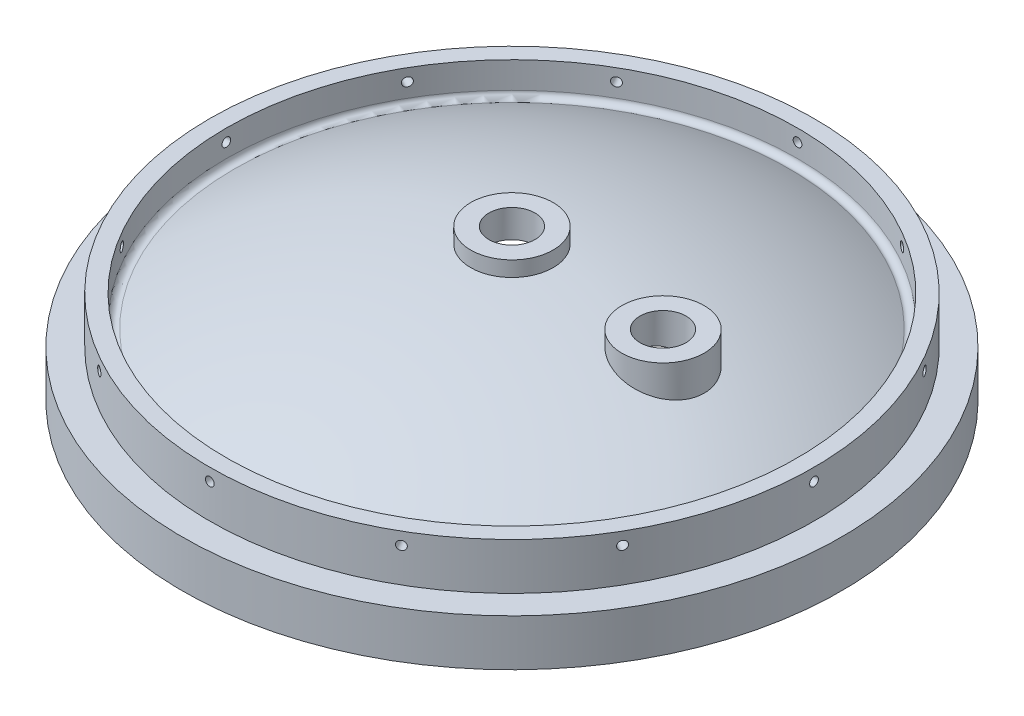
SolidWorks part; units mm, degrees
material "6061-T6 (SS)"
ref_plane "Front Plane" through (0, 0, 0) normal (0, 0, 1) x (1, 0, 0)
ref_plane "Top Plane" through (0, 0, 0) normal (0, 1, 0) x (1, 0, 0)
ref_plane "Right Plane" through (0, 0, 0) normal (1, 0, 0) x (0, 0, -1)
sketch "Sketch1" plane through (0, 0, 0) normal (0, 0, 1) x (1, 0, 0)
  line L0 (146.05, 0) -> (152.4, 0)
  line L1 (152.4, 0) -> (152.4, 21.59)
  line L2 (152.4, 21.59) -> (139.7, 21.59)
  line L3 (139.7, 21.59) -> (139.7, 43.18)
  line L4 (0, 63.5) -> (0, 57.15)
  line L5 (146.05, 0) -> (146.05, 9.4998)
  line L6 (139.7, 43.18) -> (132.08, 43.18)
  line L7 (132.08, 43.18) -> (132.08, 26.4582)
  arc A0 (0, 63.5) -> (132.08, 26.4582) centre (0, -190.5) cw
  arc A1 (0, 57.15) -> (146.05, 9.4998) centre (0, -190.5) cw
  dimension "D1" = 152.4
  dimension "D2" = 6.35
  dimension "D9" = 7.62
  dimension "D3" = 12.7
  dimension "D4" = 21.59
  dimension "D5" = 43.18
  dimension "D6" = 6.35
  dimension "D8" = 63.5
revolve "Revolve1" add sketch "Sketch1" angle 360 about L4
ref_plane "Plane1" through (139.7, 0, 0) normal (1, 0, 0) x (0, 0, -1)
hole_wizard "Tap Drill for #10-32 Tap1" positions "Sketch4" profile "Sketch5" hole size "#10-32" standard "ANSI Inch" end condition up to next
sketch "Sketch4" plane through (139.7, 0, 0) normal (1, 0, 0) x (0, 0, -1)
  line L0 (152.4, 21.59) -> (-152.4, 21.59) construction
  point P0 (0, 37.465)
  dimension "D1" = 15.875
sketch "Sketch5" plane through (139.7, 37.465, 0) normal (0, 1, 0) x (0, 0, -1)
  line L0 (0, 0) -> (0, 42.9401)
  line L1 (0, 42.9401) -> (2.0193, 42.9401)
  line L2 (2.0193, 42.9401) -> (2.0193, 0)
  line L5 (2.0193, 0) -> (0, 0)
  line L11 (0, -6.35) -> (0, 107.95) construction
  dimension "Thru Hole Dia." = 4.0386
  dimension "Thru Hole Depth" = 42.9401
pattern_circular "CirPattern1" count 12 over 360 about axis through (0, 63.5, 0) along (0, 1, 0) of "Tap Drill for #10-32 Tap1" reverse direction yes
ref_plane "Plane2" through (0, 63.5, 0) normal (0, 1, 0) x (1, 0, 0)
sketch "Sketch7" plane through (0, 63.5, 0) normal (0, 1, 0) x (1, 0, 0)
  circle A0 centre (0, 0) radius 10.668
  circle A1 centre (0, 0) radius 69.85
  circle A2 centre (0, 69.85) radius 10.668
  circle A3 centre (0, -69.85) radius 10.668
  circle A4 centre (-69.85, 0) radius 6.604
  dimension "D1" = 21.336
  dimension "D2" = 139.7
  dimension "D3" = 21.336
  dimension "D4" = 21.336
  dimension "D5" = 13.208
extrude "Cut-Extrude1" cut sketch "Sketch7" against normal up to next contours A0 region at (0, 63.5, 0)
ref_plane "Plane3" through (0, 57.15, 0) normal (0, 1, 0) x (1, 0, 0)
ref_plane "Plane4" through (0, 69.85, 0) normal (0, 1, 0) x (1, 0, 0)
sketch "Sketch10" plane through (0, 69.85, 0) normal (0, 1, 0) x (1, 0, 0)
  circle A0 centre (0, 0) radius 19.05
  circle A1 centre (0, 0) radius 10.668
  dimension "D1" = 38.1
extrude "Boss-Extrude2" add sketch "Sketch10" against normal up to next
ref_plane "Plane5" through (0, 63.5, 0) normal (0, 1, 0) x (1, 0, 0)
sketch "Sketch11" plane through (0, 63.5, 0) normal (0, 1, 0) x (1, 0, 0)
  circle A0 centre (0, 0) radius 69.85
  circle A1 centre (69.85, 0) radius 10.668
  dimension "D1" = 139.7
  dimension "D2" = 21.336
extrude "Cut-Extrude2" cut sketch "Sketch11" against normal through all contours A0 A1 | A0 A1 region at (65.1788, 63.5, 0) region at (74.2277, 63.5, 0)
sketch "Sketch13" plane through (0, 63.5, 0) normal (0, 1, 0) x (1, 0, 0)
  circle A0 centre (69.85, 0) radius 19.05
  circle A1 centre (69.85, 0) radius 10.668
  dimension "D1" = 38.1
extrude "Boss-Extrude3" add sketch "Sketch13" against normal up to next
fillet "Fillet1" radius 2.54 1 edges at (-132.08, 26.4582, 0)
